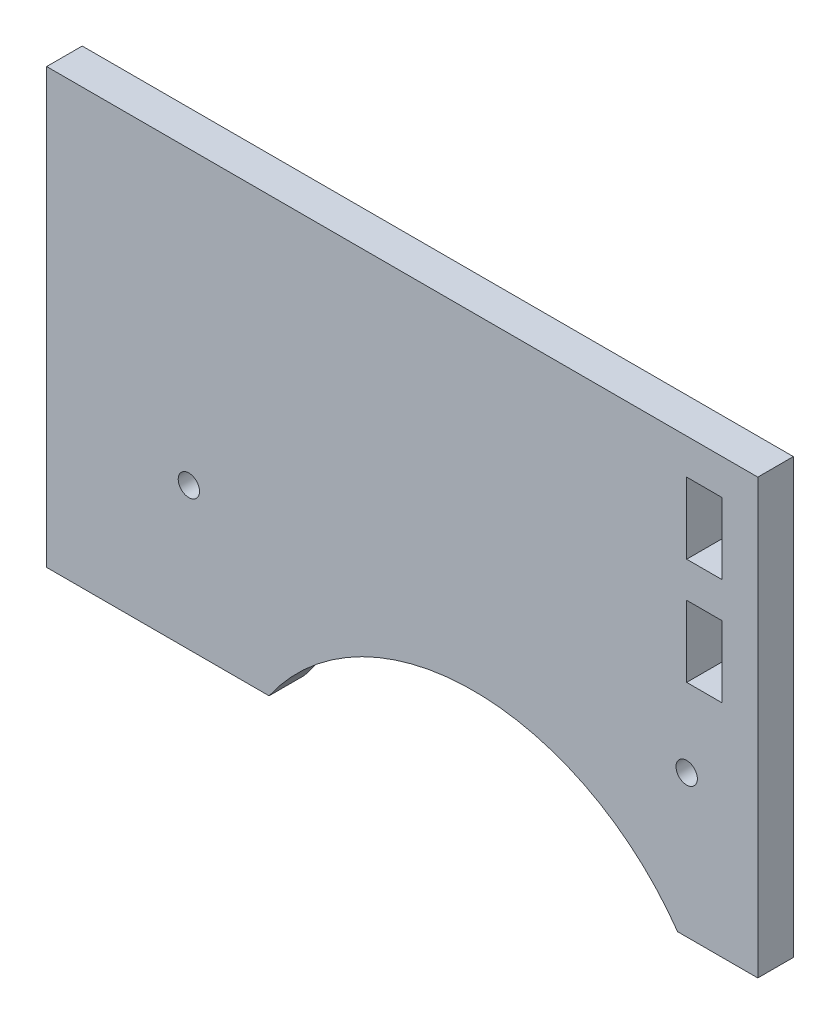
SolidWorks part; units mm, degrees
ref_plane "Plan de face" through (0, 0, 0) normal (0, 0, 1) x (1, 0, 0)
ref_plane "Plan de dessus" through (0, 0, 0) normal (0, 1, 0) x (1, 0, 0)
ref_plane "Plan de droite" through (0, 0, 0) normal (1, 0, 0) x (0, 0, -1)
sketch "Esquisse1" plane through (0, 0, 0) normal (0, 0, 1) x (1, 0, 0)
  line L0 (20, 71) -> (20, 0) construction
  line L1 (0, 0) -> (31.2772, 0)
  line L2 (0, 0) -> (0, 61)
  line L3 (0, 61) -> (100, 61)
  line L4 (100, 0) -> (100, 61)
  line L6 (90, 56) -> (95, 56)
  line L7 (90, 56) -> (90, 46)
  line L8 (90, 46) -> (95, 46)
  line L9 (95, 56) -> (95, 46)
  line L10 (20, 20) -> (90, 20) construction
  line L11 (88.7228, 0) -> (100, 0)
  line L12 (90, 41) -> (95, 41)
  line L13 (90, 41) -> (90, 31)
  line L14 (90, 31) -> (95, 31)
  line L15 (95, 41) -> (95, 31)
  circle A4 centre (20, 20) radius 1.5
  circle A5 centre (20, 20) radius 1.5 construction
  circle A6 centre (90, 20) radius 1.5
  circle A7 centre (60, -20) radius 35 construction
  arc A8 (31.2772, 0) -> (88.7228, 0) centre (60, -20) cw
  dimension "D6" = 5
  dimension "D8" = 10
  dimension "D9" = 3
  dimension "D10" = 70
  dimension "D13" = 70
  dimension "D2" = 20
  dimension "D3" = 61
  dimension "D4" = 20
  dimension "D5" = 100
  dimension "D7" = 5
  dimension "D11" = 5
  dimension "D12" = 5
  dimension "D14" = 40
  dimension "D15" = 40
extrude "Boss.-Extru.1" add sketch "Esquisse1" along normal blind 5
